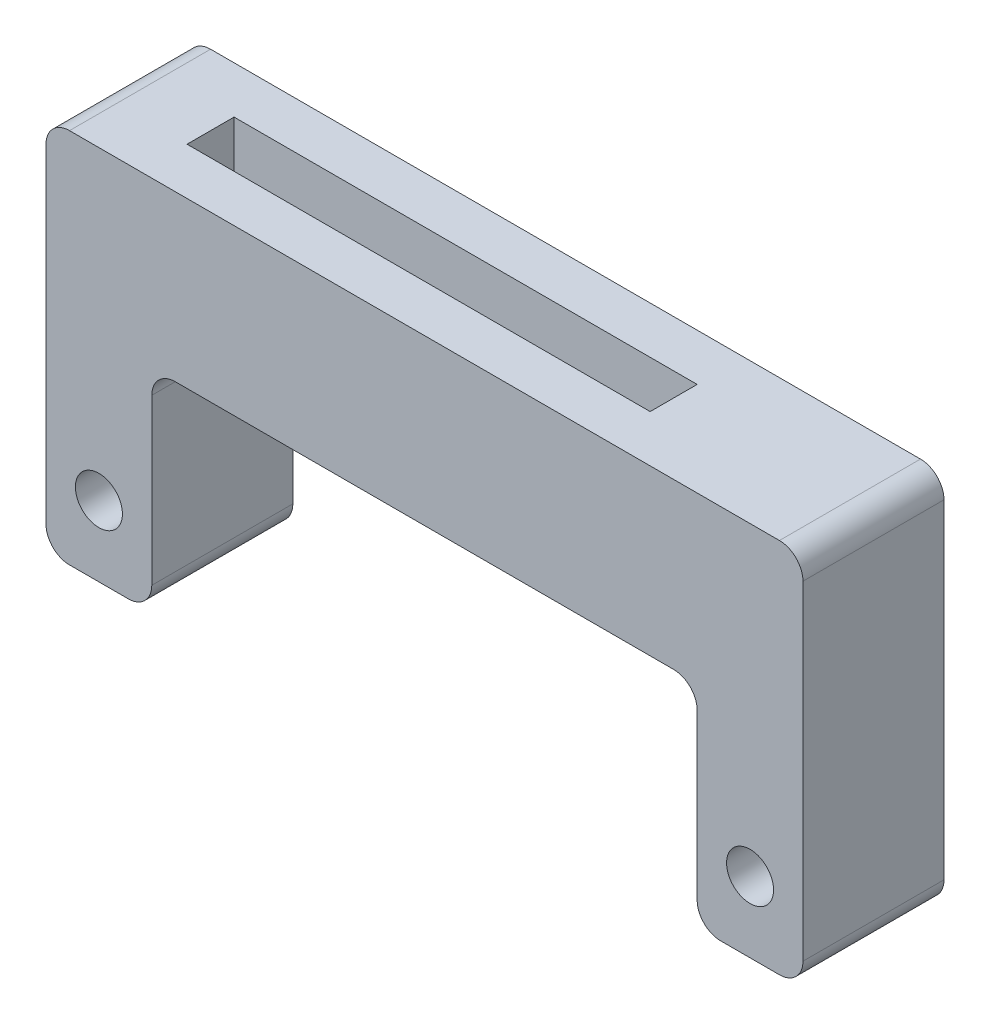
SolidWorks part; units mm, degrees
ref_plane "Front Plane" through (0, 0, 0) normal (0, 0, 1) x (1, 0, 0)
ref_plane "Top Plane" through (0, 0, 0) normal (0, 1, 0) x (1, 0, 0)
ref_plane "Right Plane" through (0, 0, 0) normal (1, 0, 0) x (0, 0, -1)
sketch "Sketch2" plane through (0, 0, 0) normal (0, 0, 1) x (1, 0, 0)
  line L1 (-16.1, -8) -> (16.1, -8)
  line L2 (-16.1, -8) -> (-16.1, 8)
  line L3 (-16.1, 8) -> (16.1, 8)
  line L4 (16.1, -8) -> (16.1, 8)
  line L5 (-16.1, -8) -> (16.1, 8) construction
  line L6 (-16.1, 8) -> (16.1, -8) construction
  point P0 (0, 0)
  dimension "D1" = 16
  dimension "D2" = 32.2
extrude "Boss-Extrude1" add sketch "Sketch2" along normal mid plane 6
sketch "Sketch3" plane through (0, 8, 0) normal (0, 1, 0) x (1, 0, 0)
  line L0 (-16.1, -3) -> (-16.1, 3) construction
  line L1 (-12.1, 1) -> (7.6, 1)
  line L2 (-12.1, 1) -> (-12.1, -1)
  line L3 (-12.1, -1) -> (7.6, -1)
  line L4 (7.6, 1) -> (7.6, -1)
  line L5 (16.1, -3) -> (16.1, 3) construction
  line L6 (16.1, 3) -> (-16.1, 3) construction
  dimension "D1" = 2
  dimension "D2" = 4
  dimension "D3" = 8.5
  dimension "D4" = 2
extrude "Cut-Extrude1" cut sketch "Sketch3" against normal blind 4
sketch "Sketch4" plane through (0, 0, 3) normal (0, 0, 1) x (1, 0, 0)
  line L0 (-16.1, -8) -> (16.1, -8) construction
  line L1 (-11.6, -8) -> (11.6, -8)
  line L2 (-11.6, -8) -> (-11.6, 1)
  line L3 (-11.6, 1) -> (11.6, 1)
  line L4 (11.6, -8) -> (11.6, 1)
  line L5 (-16.1, 8) -> (-16.1, -8) construction
  line L6 (16.1, -8) -> (16.1, 8) construction
  dimension "D1" = 9
  dimension "D2" = 4.5
  dimension "D3" = 4.5
extrude "Cut-Extrude2" cut sketch "Sketch4" against normal through all
sketch "Sketch5" plane through (0, 0, 3) normal (0, 0, 1) x (1, 0, 0)
  line L0 (-16.1, 8) -> (-16.1, -8) construction
  line L1 (16.1, -8) -> (16.1, 8) construction
  line L2 (-16.1, -8) -> (-11.6, -8) construction
  circle A0 centre (-13.85, -5) radius 1
  circle A2 centre (13.85, -5) radius 1
  point P4 (0, 0)
  point P5 (0, 0)
  dimension "D1" = 2
  dimension "D2" = 2.25
  dimension "D3" = 2.25
  dimension "D4" = 3
extrude "Cut-Extrude3" cut sketch "Sketch5" against normal through all
fillet "Fillet1" radius 1 8 edges at (16.1, 8, 0) (16.1, -8, 0) (11.6, -8, 0) (11.6, 1, 0) (-11.6, 1, 0) (-11.6, -8, 0) (-16.1, -8, 0) (-16.1, 8, 0)
